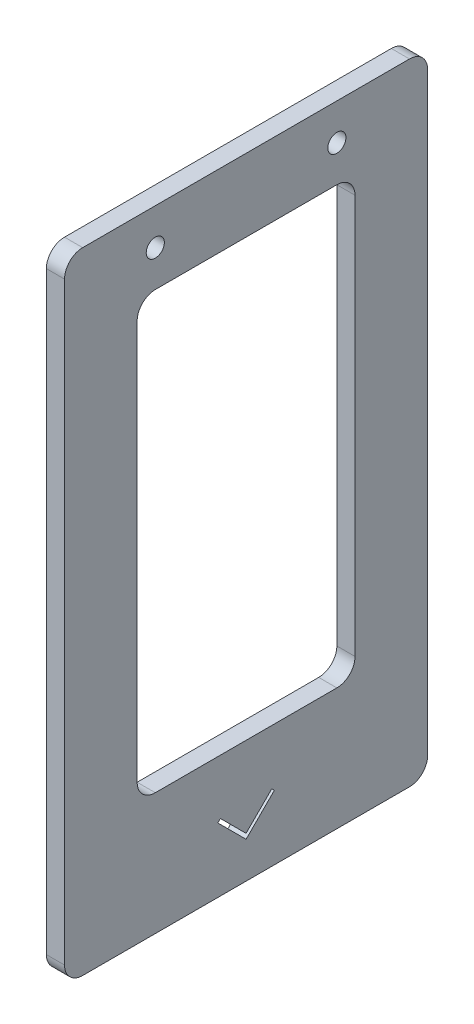
SolidWorks part; units mm, degrees
material "Balsa"
ref_plane "Front Plane" through (0, 0, 0) normal (0, 0, 1) x (1, 0, 0)
ref_plane "Top Plane" through (0, 0, 0) normal (0, 1, 0) x (1, 0, 0)
ref_plane "Right Plane" through (0, 0, 0) normal (1, 0, 0) x (0, 0, -1)
sketch "Sketch3" plane through (0, 0, 0) normal (1, 0, 0) x (0, 0, -1)
  line L0 (-31.75, -67.564) -> (31.75, -67.564)
  line L1 (-57.15, -110.236) -> (57.15, -110.236)
  line L2 (-63.5, -103.886) -> (-63.5, 103.886)
  line L3 (-57.15, 110.236) -> (57.15, 110.236)
  line L4 (63.5, -103.886) -> (63.5, 103.886)
  line L5 (-63.5, -110.236) -> (63.5, 110.236) construction
  line L6 (-63.5, 110.236) -> (63.5, -110.236) construction
  line L8 (-38.1, -61.214) -> (-38.1, 78.486)
  line L9 (-31.75, 84.836) -> (31.75, 84.836)
  line L11 (0, 0) -> (38.1, 84.836) construction
  line L12 (-38.1, 84.836) -> (0, 0) construction
  line L13 (38.1, -61.214) -> (38.1, 78.486)
  arc A0 (-57.15, -110.236) -> (-63.5, -103.886) centre (-57.15, -103.886) cw
  arc A1 (63.5, -103.886) -> (57.15, -110.236) centre (57.15, -103.886) cw
  arc A2 (63.5, 103.886) -> (57.15, 110.236) centre (57.15, 103.886) ccw
  arc A3 (-63.5, 103.886) -> (-57.15, 110.236) centre (-57.15, 103.886) cw
  arc A4 (31.75, -67.564) -> (38.1, -61.214) centre (31.75, -61.214) ccw
  arc A5 (-31.75, -67.564) -> (-38.1, -61.214) centre (-31.75, -61.214) cw
  arc A6 (31.75, 84.836) -> (38.1, 78.486) centre (31.75, 78.486) cw
  arc A7 (-38.1, 78.486) -> (-31.75, 84.836) centre (-31.75, 78.486) cw
  point P0 (0, 0)
  point P6 (0, 0)
  point P26 (38.1, -67.564)
  dimension "D7" = 6.35
  dimension "D8" = 6.35
  dimension "D1" = 220.472
  dimension "D2" = 127
  dimension "D3" = 76.2
  dimension "D4" = 152.4
  dimension "D5" = 25.4
  dimension "D6" = 25.4
extrude "Boss-Extrude2" add sketch "Sketch3" along normal blind 6.35
sketch "Sketch4" plane through (6.35, 0, 0) normal (1, 0, 0) x (0, 0, -1)
  line L0 (-57.15, -110.236) -> (57.15, -110.236) construction
  line L5 (0, -95.7399) -> (-8.9803, -86.7597)
  line L6 (-8.9803, -86.7597) -> (-9.8783, -87.6577)
  line L8 (-9.8783, -87.6577) -> (0, -97.536)
  line L9 (0, -97.536) -> (9.8783, -87.6577)
  line L10 (9.8783, -87.6577) -> (8.9803, -86.7597)
  line L11 (8.9803, -86.7597) -> (0, -95.7399)
  line L12 (0, 3.4925) -> (0, -3.4925) construction
  dimension "D1" = 12.7
  dimension "D2" = 12.7
  dimension "D3" = 1.27
extrude "Cut-Extrude1" cut sketch "Sketch4" against normal up to next
sketch "Sketch5" plane through (6.35, 0, 0) normal (1, 0, 0) x (0, 0, -1)
  line L0 (-31.75, 97.536) -> (31.75, 97.536) construction
  line L1 (31.75, 97.536) -> (63.5, 97.536) construction
  line L2 (63.5, -103.886) -> (63.5, 103.886) construction
  line L3 (-31.75, 97.536) -> (-63.5, 97.536) construction
  line L4 (-63.5, 103.886) -> (-63.5, -103.886) construction
  line L5 (57.15, 110.236) -> (-57.15, 110.236) construction
  circle A0 centre (-31.75, 97.536) radius 3.175
  circle A1 centre (31.75, 97.536) radius 3.175
  point P12 (-37.9423, 97.536)
  dimension "D1" = 6.35
  dimension "D2" = 63.5
  dimension "D3" = 12.7
extrude "Cut-Extrude2" cut sketch "Sketch5" against normal through all both and the other way through all
